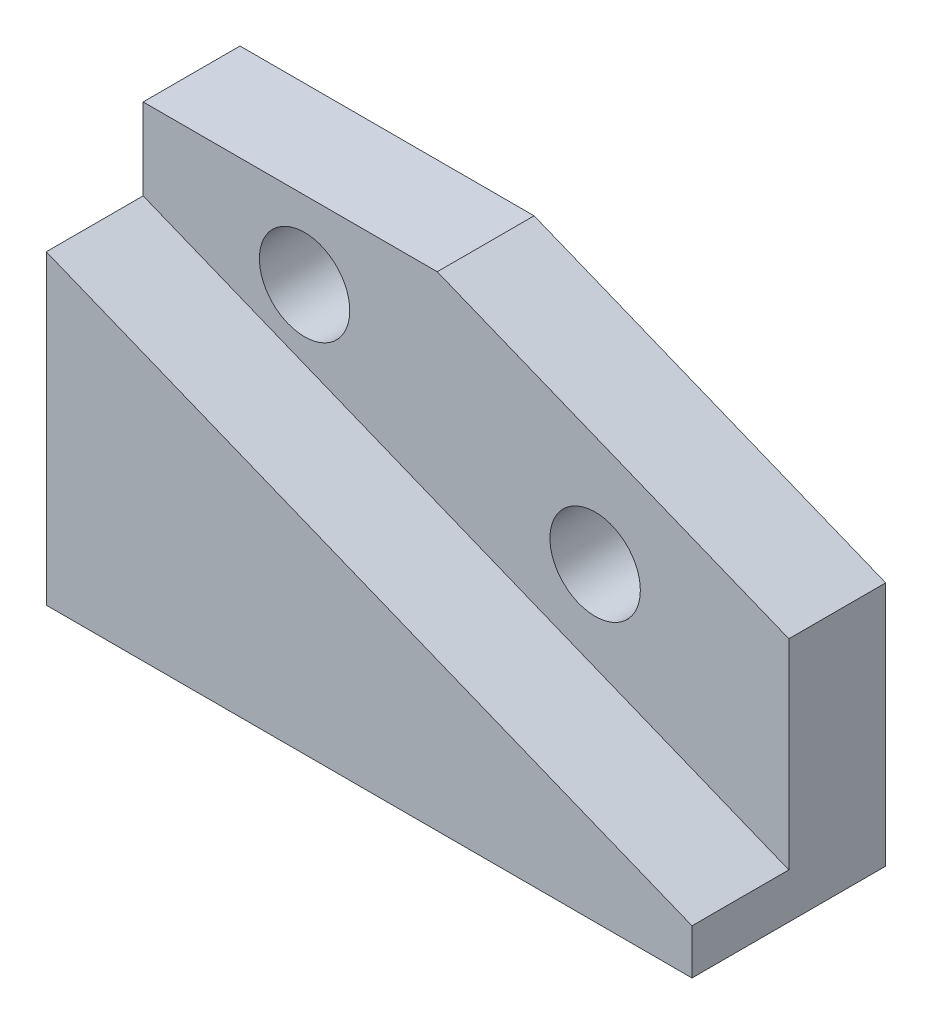
SolidWorks part; units mm, degrees
ref_plane "Front Plane" through (0, 0, 0) normal (0, 0, 1) x (1, 0, 0)
ref_plane "Top Plane" through (0, 0, 0) normal (0, 1, 0) x (1, 0, 0)
ref_plane "Right Plane" through (0, 0, 0) normal (1, 0, 0) x (0, 0, -1)
sketch "Sketch1" plane through (0, 0, 0) normal (0, 0, 1) x (1, 0, 0)
  line L1 (0, 0) -> (100, 0)
  line L3 (0, 60) -> (45.5481, 60)
  line L4 (45.5481, 60) -> (100, 38)
  line L5 (0, 47.4026) -> (100, 7)
  line L6 (100, 38) -> (100, 7)
  line L7 (0, 60) -> (0, 47.4026)
  line L8 (100, 38) -> (100, 7)
  line L9 (100, 7) -> (100, 0)
  line L10 (0, 47.4026) -> (0, 0)
  circle A0 centre (25, 48) radius 7
  circle A1 centre (70, 33) radius 7
  point P11 (0, 0)
  dimension "D7" = 14
  dimension "D1" = 60
  dimension "D2" = 68
  dimension "D3" = 38
  dimension "D4" = 7
  dimension "D5" = 100
  dimension "D6" = 22
  dimension "D8" = 12
  dimension "D9" = 25
  dimension "D10" = 27
  dimension "D11" = 30
extrude "Boss-Extrude1" add sketch "Sketch1" along normal blind 30 contours L5 L10 L1 L9 region at (37.6223, 16.1011, 0)
extrude "Boss-Extrude2" add sketch "Sketch1<3>" along normal blind 15 contours L3 L7 L5 L6 L4 A1 A0 region at (56.4735, 38.8484, 0)
sketch "Sketch1<3>" plane through (0, 0, 0) normal (0, 0, 1) x (1, 0, 0) same geometry as "Sketch1"
